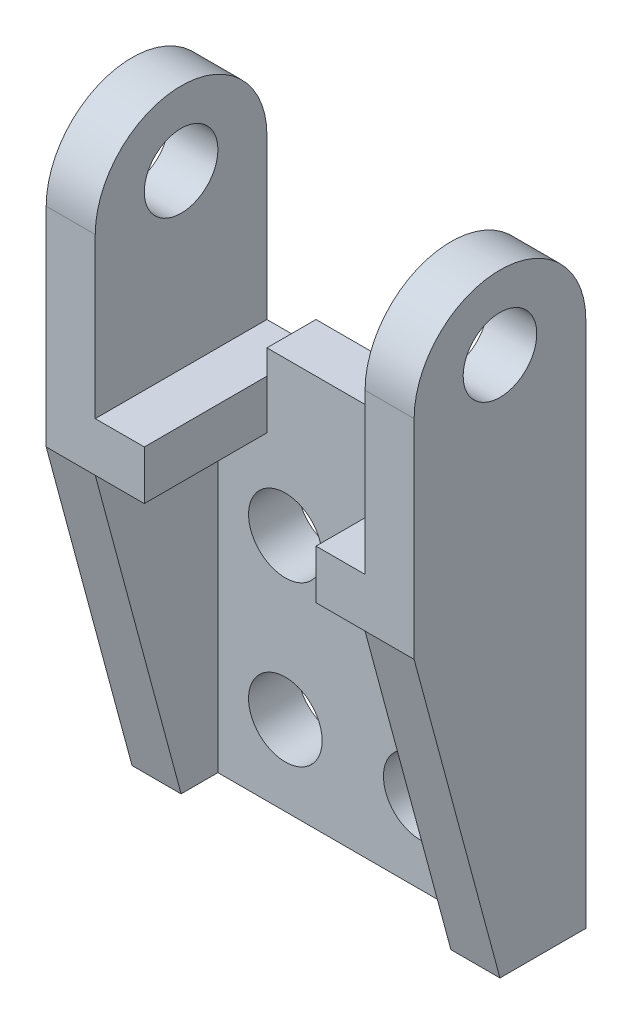
SolidWorks part; units mm, degrees
ref_plane "Спереди" through (0, 0, 0) normal (0, 0, 1) x (1, 0, 0)
ref_plane "Сверху" through (0, 0, 0) normal (0, 1, 0) x (1, 0, 0)
ref_plane "Справа" through (0, 0, 0) normal (1, 0, 0) x (0, 0, -1)
sketch "Эскиз1" plane through (0, 0, 0) normal (0, 0, 1) x (1, 0, 0)
  line L1 (-7.5, 12.5) -> (7.5, 12.5)
  line L2 (-7.5, 12.5) -> (-7.5, -12.5)
  line L3 (-7.5, -12.5) -> (7.5, -12.5)
  line L4 (7.5, 12.5) -> (7.5, -12.5)
  line L5 (-7.5, 12.5) -> (7.5, -12.5) construction
  line L6 (-7.5, -12.5) -> (7.5, 12.5) construction
  point P0 (0, 0)
  dimension "D1" = 15
  dimension "D2" = 25
extrude "Бобышка-Вытянуть1" add sketch "Эскиз1" along normal blind 7
sketch "Эскиз2" plane through (0, 0, 7) normal (0, 0, 1) x (1, 0, 0)
  line L0 (-7.5, 12.5) -> (-5.5, 12.5)
  line L1 (7.5, 12.5) -> (-7.5, 12.5) construction
  line L2 (-5.5, 12.5) -> (-5.5, -12.5)
  line L3 (-7.5, -12.5) -> (7.5, -12.5) construction
  line L4 (-5.5, -12.5) -> (5.5, -12.5)
  line L5 (5.5, -12.5) -> (5.5, 12.5)
  line L6 (5.5, 12.5) -> (7.5, 12.5)
  line L7 (7.5, 12.5) -> (-7.5, 12.5)
  line L8 (-5.5, -12.5) -> (-5.5, 0.5)
  line L9 (-5.5, 0.5) -> (-3.5, 0.5)
  line L10 (-3.5, 0.5) -> (-3.5, 12.5)
  line L11 (-3.5, 12.5) -> (3.5, 12.5)
  line L12 (3.5, 12.5) -> (5.5, 12.5)
  line L13 (3.5, 12.5) -> (3.5, 0.5)
  line L14 (3.5, 0.5) -> (5.5, 0.5)
  line M6 (-7.5, -12.5) -> (7.5, -12.5)
  dimension "D1" = 2
  dimension "D2" = 2
  dimension "D3" = 12
extrude "Вырез-Вытянуть1" cut sketch "Эскиз2" against normal blind 5 contours L14 L13 L7 L10 L9 L2 L5 M6 region at (0, -1.3744, 7)
sketch "Эскиз3" plane through (0, 0, 7) normal (0, 0, 1) x (1, 0, 0)
  line L0 (-7.5, 12.5) -> (-5.5, 12.5)
  line L1 (-3.5, 12.5) -> (-7.5, 12.5) construction
  line L2 (-5.5, 12.5) -> (-5.5, 2.5)
  line L3 (-5.5, 2.5) -> (-7.5, 2.5)
  line L4 (-7.5, 12.5) -> (-7.5, -12.5) construction
  line L5 (-7.5, 2.5) -> (-7.5, 12.5)
  line L6 (0, 13.2014) -> (0, 4.2809)
  line L7 (7.5, 2.5) -> (7.5, 12.5)
  line L8 (5.5, 2.5) -> (7.5, 2.5)
  line L9 (5.5, 12.5) -> (5.5, 2.5)
  line L10 (7.5, 12.5) -> (5.5, 12.5)
  line M5 (7.5, -12.5) -> (7.5, 12.5)
  line M6 (7.5, 12.5) -> (3.5, 12.5)
  dimension "D1" = 10
extrude "Вырез-Вытянуть2" cut sketch "Эскиз3" against normal blind 13 contours L5 L3 L2 L0 | L9 L8 M6 M5 region at (-6.5, 7.5, 7) region at (6.5, 7.5, 7)
sketch "Эскиз4" plane through (-5.5, 0, 0) normal (-1, 0, 0) x (0, 0, 1)
  line L0 (7, 12.5) -> (5, 12.5)
  line L1 (0, 12.5) -> (7, 12.5) construction
  line L2 (5, 12.5) -> (5, 9.5)
  line L3 (5, 9.5) -> (7, 9.5)
  line L4 (7, 12.5) -> (7, 2.5) construction
  line L5 (3.5, 12.5) -> (3.5, 9.5219)
  line L6 (2, 9.5) -> (0, 9.5)
  line L7 (2, 12.5) -> (2, 9.5)
  line L8 (0, 12.5) -> (2, 12.5)
  line L9 (7, 12.5) -> (7, 9.5)
  line L10 (0, 9.5) -> (0, 12.5)
  line M4 (0, 12.5) -> (0, 2.5)
  line M6 (7, 2.5) -> (7, 12.5)
  line M7 (7, 12.5) -> (0, 12.5)
  dimension "D1" = 2
  dimension "D2" = 3
extrude "Вырез-Вытянуть3" cut sketch "Эскиз4" against normal through all contours L2 L3 M6 M7 | L7 L6 M7 M4 region at (-5.5, 11, 6) region at (-5.5, 11, 1)
sketch "Эскиз5" plane through (0, 0, 2) normal (0, 0, 1) x (1, 0, 0)
  line L0 (-3.5, 0.5) -> (-3.5, 9.5) construction
  line L1 (3.5, 9.5) -> (-3.5, 9.5)
  line L2 (3.5, 9.5) -> (3.5, 3.5)
  line L3 (3.5, 3.5) -> (-3.5, 3.5)
  line L4 (-3.5, 9.5) -> (-3.5, 3.5)
  dimension "D1" = 6
extrude "Вырез-Вытянуть4" cut sketch "Эскиз5" against normal blind 13
sketch "Эскиз6" plane through (-5.5, 0, 0) normal (-1, 0, 0) x (0, 0, 1)
  line L0 (5, 9.5) -> (3.5, 9.5)
  circle A0 centre (3.5, 9.5) radius 1.5
  dimension "D1" = 3
extrude "Бобышка-Вытянуть2" add sketch "Эскиз6" along normal blind 2 contours A0 region at (-5.5, 9.5, 2.0424)
sketch "Эскиз7" plane through (5.5, 0, 0) normal (1, 0, 0) x (0, 0, -1)
  line L0 (-2, 9.5) -> (-3.5, 9.5)
  circle A0 centre (-3.5, 9.5) radius 1.5
  dimension "D1" = 3
extrude "Бобышка-Вытянуть3" add sketch "Эскиз7" along normal blind 2 contours A0 region at (5.5, 9.5, 4.9576)
sketch "Эскиз8" plane through (-7.5, 0, 0) normal (-1, 0, 0) x (0, 0, 1)
  line L0 (7, 0.5) -> (3.5, -12.5)
  line L1 (7, -12.5) -> (0, -12.5) construction
  line L2 (3.5, -12.5) -> (7, -12.5)
  line L3 (7, -12.5) -> (7, 0.5)
extrude "Вырез-Вытянуть5" cut sketch "Эскиз8" against normal through all
sketch "Эскиз9" plane through (0, 0, 2) normal (0, 0, 1) x (1, 0, 0)
  line L1 (5.5, -12.5) -> (5.5, 0.5)
  circle A0 centre (-2.75, -2.75) radius 1.5
  circle A1 centre (-2.75, -9.25) radius 1.5
  circle A2 centre (2.75, -2.75) radius 1.5
  circle A3 centre (2.75, -9.25) radius 1.5
  dimension "D1" = 3
extrude "Вырез-Вытянуть6" cut sketch "Эскиз9" against normal through all contours A0 | A2 | A1 | A3 region at (-2.75, -2.75, 2) region at (-2.75, -9.25, 2) region at (2.75, -2.75, 2) region at (2.75, -9.25, 2)
sketch "Эскиз10" plane through (0, 0, 7) normal (0, 0, 1) x (1, 0, 0)
  line L1 (-7.5, 2.5) -> (-3.5, 2.5)
  line L2 (-7.5, 2.5) -> (-7.5, 12.5)
  line L3 (-7.5, 12.5) -> (-3.5, 12.5)
  line L4 (-3.5, 2.5) -> (-3.5, 12.5)
  line L5 (7.5, 2.5) -> (3.5, 2.5)
  line L6 (7.5, 2.5) -> (7.5, 12.5)
  line L7 (7.5, 12.5) -> (3.5, 12.5)
  line L8 (3.5, 2.5) -> (3.5, 12.5)
extrude "Бобышка-Вытянуть5" add sketch "Эскиз10" against normal blind 7
sketch "Эскиз12" plane through (0, 0, 7) normal (0, 0, 1) x (1, 0, 0)
  line L0 (3.5, 0.5) -> (3.5, 2.5)
  line L1 (3.5, 12.5) -> (3.5, 0.5) construction
  line L2 (3.5, 2.5) -> (5.5, 2.5)
  line L3 (5.5, 2.5) -> (5.5, 12.5)
  line L4 (7.5, 12.5) -> (3.5, 12.5) construction
  line L5 (5.5, 12.5) -> (3.5, 12.5)
  line L6 (3.5, 12.5) -> (3.5, 2.5)
  line L7 (0, 3.5) -> (0, 2.0319)
  line L8 (-3.5, 3.5) -> (3.5, 3.5) construction
  line L9 (-3.5, 12.5) -> (-3.5, 2.5)
  line L10 (-5.5, 12.5) -> (-3.5, 12.5)
  line L11 (-5.5, 2.5) -> (-5.5, 12.5)
  line L12 (-3.5, 2.5) -> (-5.5, 2.5)
  line L13 (-3.5, 0.5) -> (-3.5, 2.5)
  line M4 (3.5, 12.5) -> (3.5, 0.5)
  line M8 (7.5, 12.5) -> (3.5, 12.5)
  dimension "D1" = 2
  dimension "D2" = 2
extrude "Вырез-Вытянуть7" cut sketch "Эскиз12" against normal through all contours L2 L3 M8 M4 | L12 L9 L10 L11 region at (4.5, 7.5, 7) region at (-4.5, 7.5, 7)
sketch "Эскиз14" plane through (-7.5, 0, 0) normal (-1, 0, 0) x (0, 0, 1)
  line L0 (3.5, 12.5) -> (3.5, 9.5)
  line L1 (0, 12.5) -> (7, 12.5) construction
  circle A0 centre (3.5, 9.5) radius 1.5
  dimension "D2" = 3
  dimension "D1" = 3
extrude "Вырез-Вытянуть9" cut sketch "Эскиз14" against normal through all contours A0 region at (-7.5, 8.4693, 2.4693)
fillet "Скругление1" 2 edges at (-6.5, 12.5, 7) (-6.5, 12.5, 0) type full round first side face at (-5.5, 4.5, 7) second side face at (-1.25, -2.75, 0) middle face at (-6.5, 12.5, 3.5)
fillet "Скругление2" 2 edges at (6.5, 12.5, 7) (6.5, 12.5, 0) type full round first side face at (5.5, 4.5, 7) second side face at (-1.25, -2.75, 0) middle face at (6.5, 12.5, 3.5)
